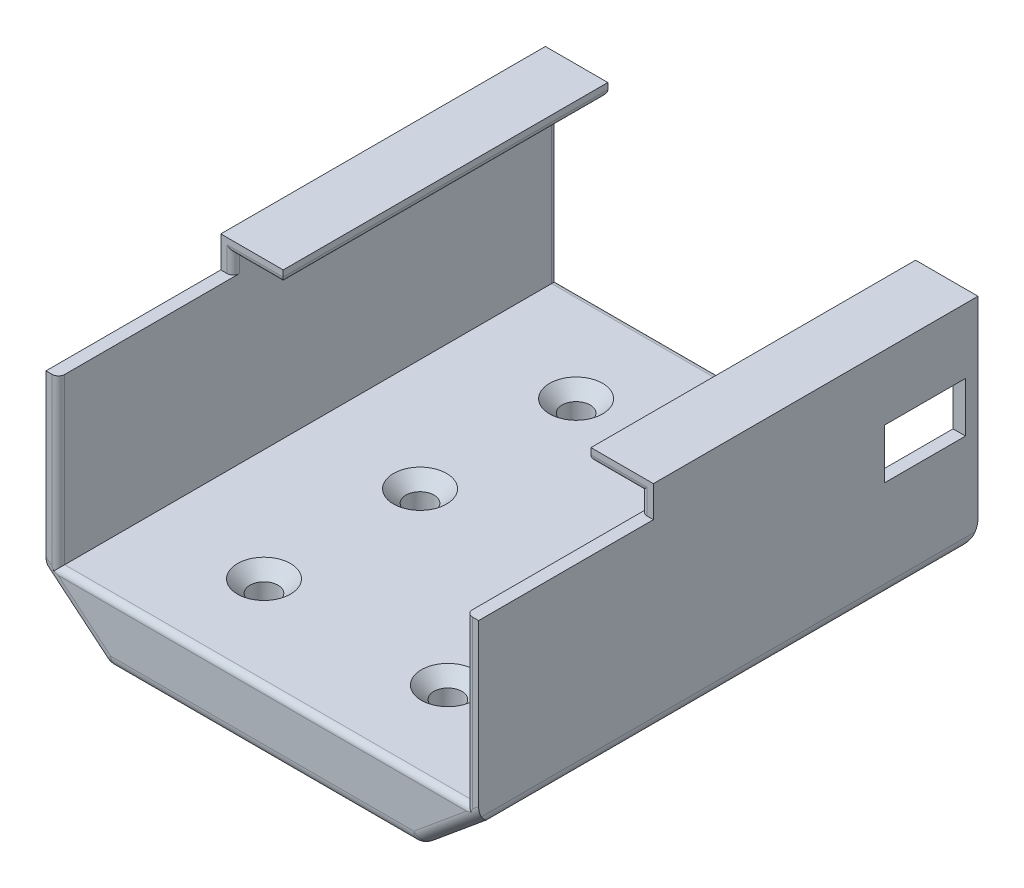
SolidWorks part; units mm, degrees
ref_plane "Front Plane" through (0, 0, 0) normal (0, 0, 1) x (1, 0, 0)
ref_plane "Top Plane" through (0, 0, 0) normal (0, 1, 0) x (1, 0, 0)
ref_plane "Right Plane" through (0, 0, 0) normal (1, 0, 0) x (0, 0, -1)
sketch "Sketch1" plane through (0, 0, 0) normal (0, 1, 0) x (1, 0, 0)
  line L1 (-25, 40) -> (25, 40)
  line L2 (-25, 40) -> (-25, -40)
  line L3 (-25, -40) -> (25, -40)
  line L4 (25, 40) -> (25, -40)
  line L5 (-25, 40) -> (25, -40) construction
  line L6 (-25, -40) -> (25, 40) construction
  point P0 (0, 0)
  dimension "D1" = 50
  dimension "D2" = 80
extrude "Boss-Extrude1" add sketch "Sketch1" along normal blind 10
sketch "Sketch2" plane through (0, 10, 0) normal (0, 1, 0) x (1, 0, 0)
  line L0 (0, 40) -> (0, -40) construction
  line L1 (25, 40) -> (-25, 40) construction
  line L2 (-25, -40) -> (25, -40) construction
  line L3 (-14.7304, 40) -> (-14.7304, -40) construction
  circle A0 centre (-14.7304, 0) radius 2.25
  circle A1 centre (-14.7304, 25) radius 2.25
  circle A2 centre (-14.7304, -25) radius 2.25
  circle A3 centre (14.7304, -25) radius 2.25
  circle A4 centre (14.7304, 0) radius 2.25
  circle A5 centre (14.7304, 25) radius 2.25
  dimension "D1" = 4.5
  dimension "D2" = 25
  dimension "D3" = 25
extrude "Cut-Extrude1" cut sketch "Sketch2" against normal through all
chamfer "Chamfer1" distance 2 angle 45 6 edges at (14.7304, 10, 22.75) (-14.7304, 10, 27.25) (-14.7304, 10, 2.25) (14.7304, 10, -2.25) (14.7304, 10, -27.25) (-14.7304, 10, -22.75)
sketch "Sketch3" plane through (0, 0, 0) normal (0, 0, 1) x (1, 0, 0)
  line L0 (0, 0) -> (0, 52.1179) construction
  line L1 (-25, 10) -> (-32.65, 10)
  line L2 (-32.65, 10) -> (-32.65, 39.4)
  line L3 (-32.65, 39.4) -> (-24.65, 39.4)
  line L4 (-24.65, 39.4) -> (-24.65, 41.4)
  line L5 (-24.65, 41.4) -> (-34.65, 41.4)
  line L6 (-34.65, 41.4) -> (-34.65, 8)
  line L7 (-34.65, 8) -> (-25, 0)
  line L8 (34.65, 8) -> (25, 0)
  line L9 (34.65, 41.4) -> (34.65, 8)
  line L10 (24.65, 41.4) -> (34.65, 41.4)
  line L11 (24.65, 39.4) -> (24.65, 41.4)
  line L12 (32.65, 39.4) -> (24.65, 39.4)
  line L13 (32.65, 10) -> (32.65, 39.4)
  line L14 (25, 10) -> (32.65, 10)
  line L15 (-25, 10) -> (-25, 0)
  line L16 (25, 10) -> (25, 0)
  dimension "D1" = 2
  dimension "D2" = 65.3
  dimension "D3" = 29.4
  dimension "D4" = 2
  dimension "D5" = 8
  dimension "D6" = 2
extrude "Boss-Extrude2" add sketch "Sketch3" along normal mid plane 80
sketch "Sketch4" plane through (0, 0, 0) normal (1, 0, 0) x (0, 0, -1)
  line L0 (-40, 41.4) -> (-12, 41.4)
  line L1 (-40, 41.4) -> (40, 41.4) construction
  line L2 (-12, 41.4) -> (-12, 36.4)
  line L3 (-12, 36.4) -> (-40, 36.4)
  line L4 (-40, 8) -> (-40, 41.4) construction
  line L5 (-40, 36.4) -> (-40, 41.4)
  dimension "D1" = 28
  dimension "D2" = 5
extrude "Cut-Extrude2" cut sketch "Sketch4" against normal through all both and the other way through all
sketch "Sketch5" plane through (34.65, 0, 0) normal (1, 0, 0) x (0, 0, -1)
  line L1 (25, 31) -> (38, 31)
  line L2 (25, 31) -> (25, 23)
  line L3 (25, 23) -> (38, 23)
  line L4 (38, 31) -> (38, 23)
extrude "Cut-Extrude3" cut sketch "Sketch5" against normal up to next
fillet "Fillet1" radius 1 14 edges at (28.65, 39.4, 12) (28.65, 39.4, -40) (-28.65, 39.4, 12) (-28.65, 39.4, -40) (-32.65, 24.7, -40) (32.65, 24.7, -40) (0, 10, -40) (32.65, 23.2, 40) (0, 10, 40) (-32.65, 23.2, 40) (24.65, 39.4, -14) (-24.65, 39.4, -14) (-32.65, 37.9, 12) (32.65, 37.9, 12)
fillet "Fillet2" radius 2 10 edges at (-29.825, 4, 40) (29.825, 4, -40) (29.825, 4, 40) (0, 0, -40) (-29.825, 4, -40) (-34.65, 8, 0) (34.65, 8, 0) (0, 0, 40) (25, 0, 0) (-25, 0, 0)
